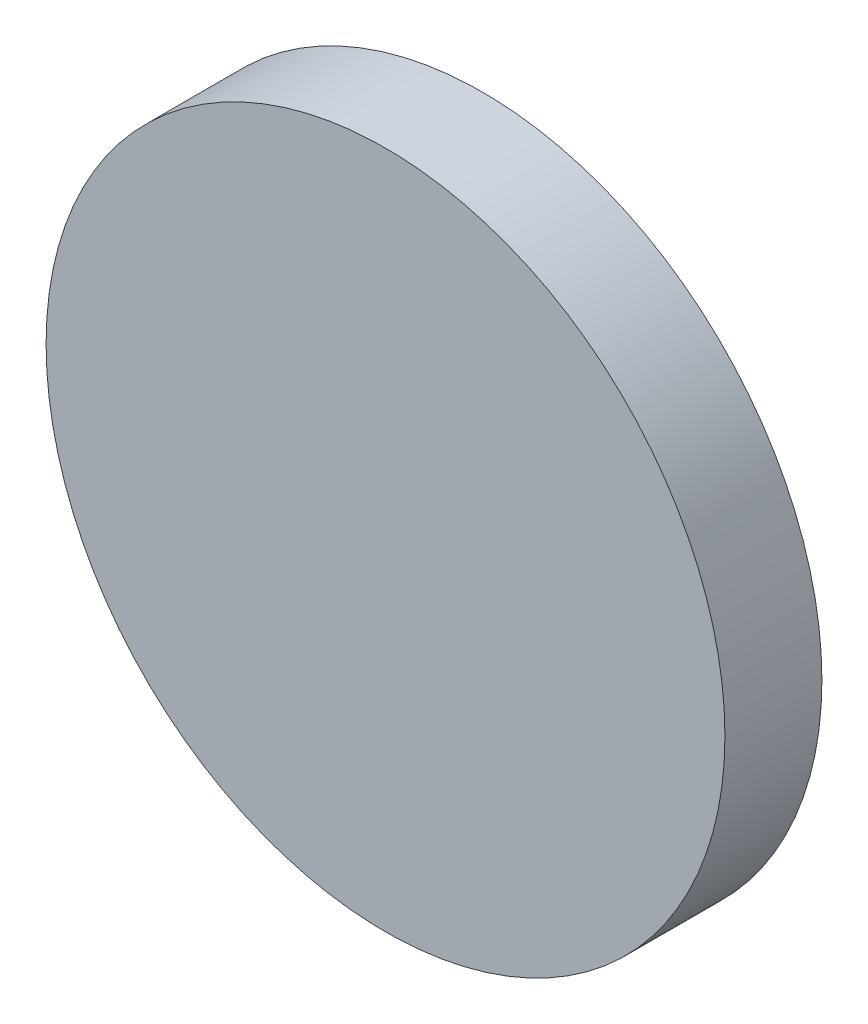
SolidWorks part; units mm, degrees
ref_plane "前基準面" through (0, 0, 0) normal (0, 0, 1) x (1, 0, 0)
ref_plane "上基準面" through (0, 0, 0) normal (0, 1, 0) x (1, 0, 0)
ref_plane "右基準面" through (0, 0, 0) normal (1, 0, 0) x (0, 0, -1)
sketch "草圖1" plane through (0, 0, 0) normal (0, 0, 1) x (1, 0, 0)
  circle A0 centre (0, 0) radius 14
  dimension "D1" = 28
extrude "填料-伸長1" add sketch "草圖1" along normal blind 4
sketch "草圖2" plane through (0, 0, 4) normal (0, 0, 1) x (1, 0, 0)
  circle A0 centre (0, 0) radius 13 construction
  circle A1 centre (0, 0) radius 11.75 construction
  dimension "D1" = 26
  dimension "D2" = 23.5
